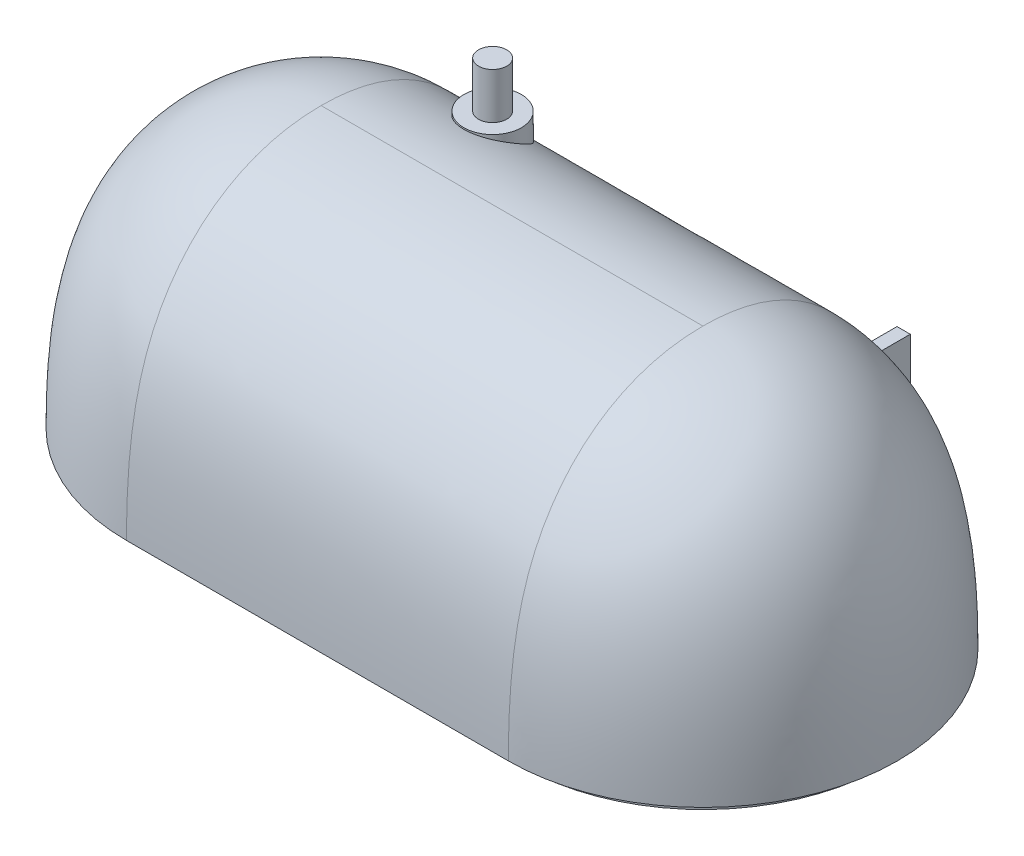
SolidWorks part; units mm, degrees
ref_plane "Front Plane" through (0, 0, 0) normal (0, 0, 1) x (1, 0, 0)
ref_plane "Top Plane" through (0, 0, 0) normal (0, 1, 0) x (1, 0, 0)
ref_plane "Right Plane" through (0, 0, 0) normal (1, 0, 0) x (0, 0, -1)
sketch "Sketch1" plane through (0, 0, 0) normal (0, 1, 0) x (1, 0, 0)
  line L0 (-41.915, 0) -> (41.915, 0) construction
  line L1 (-20.745, -21.17) -> (20.745, -21.17)
  line L2 (-20.745, -21.17) -> (-20.745, 21.17) construction
  line L3 (-20.745, 21.17) -> (20.745, 21.17)
  line L4 (20.745, -21.17) -> (20.745, 21.17) construction
  line L5 (-20.745, -21.17) -> (20.745, 21.17) construction
  line L6 (-20.745, 21.17) -> (20.745, -21.17) construction
  arc A0 (-20.745, -21.17) -> (-20.745, 21.17) centre (-20.745, 0) cw
  arc A1 (20.745, 21.17) -> (20.745, -21.17) centre (20.745, 0) cw
  point P0 (0, 0)
  dimension "D1" = 83.83
  dimension "D2" = 42.34
sketch "Sketch2" plane through (0, 0, 0) normal (1, 0, 0) x (0, 0, -1)
  line L0 (21.17, 0) -> (-21.17, 0) construction
  line L1 (21.17, 0) -> (-21.17, 0) construction
  line L2 (0, 0) -> (0, 31.55) construction
  line L3 (19.735, 0) -> (19.735, 1.19)
  line L4 (19.735, 1.19) -> (21.135, 1.19)
  line L5 (-19.735, 0) -> (19.735, 0)
  line L6 (-19.735, 1.19) -> (-21.135, 1.19)
  line L7 (-19.735, 0) -> (-19.735, 1.19)
  line L8 (18.1, 19.85) -> (18.1, 0) construction
  line L9 (18.1, 19.85) -> (-18.1, 19.85) construction
  line L10 (21.135, 1.19) -> (21.135, 0.6886) construction
  spline S0 degree 3 poles (21.135, 1.19) (21.135, 7.0764) (20.4011, 21.9995) (8.9089, 31.55) (0, 31.55) knots 0 0 0 0 0.467286 1 1 1 1
  spline S1 degree 3 poles (-21.135, 1.19) (-21.135, 7.0764) (-20.4011, 21.9995) (-8.9089, 31.55) (0, 31.55) knots 0 0 0 0 0.467286 1 1 1 1
  point P8 (0, 19.85)
  dimension "D1" = 31.55
  dimension "D2" = 39.47
  dimension "D3" = 1.19
  dimension "D4" = 1.4
  dimension "D5" = 36.2
  dimension "D6" = 19.85
extrude "Boss-Extrude2" add sketch "Sketch2" along normal up to vertex (20.745 mm away) and the other way up to vertex (20.745 mm away) up to point (20.745, 0, 21.17) other way up to point (-20.745, 0, 21.17)
sketch "Sketch4" plane through (-20.745, 0, 0) normal (-1, 0, 0) x (0, 0, 1)
  line L0 (0, 31.55) -> (0, 0)
  line L5 (-19.735, 1.19) -> (-19.735, 0)
  line L6 (-21.135, 1.19) -> (-19.735, 1.19)
  line L7 (19.735, 1.19) -> (21.135, 1.19)
  line L8 (19.735, 0) -> (19.735, 1.19)
  line L9 (-19.735, 0) -> (19.735, 0)
  line L12 (19.735, 1.19) -> (21.135, 1.19)
  line L13 (19.735, 0) -> (19.735, 1.19)
  line L14 (0, 0) -> (19.735, 0)
  spline S2 degree 3 poles (333.5549, -911.1802) (140.1511, 42.8638) (-153.2404, 81.7088) (86.9036, -145.8898) (-639.1994, 787.2913) knots -2.804305 -2.804305 -2.804305 -2.804305 0.532714 4.237911 4.237911 4.237911 4.237911 only from (0, 31.55) to (-21.135, 1.19)
  spline S3 degree 3 poles (2506.664, 3134.8984) (-251.1944, -284.8739) (340.5877, 177.8042) (-353.3586, -1.6005) (-731.6989, -3883.5105) knots -5.099916 -5.099916 -5.099916 -5.099916 0.467286 5.832152 5.832152 5.832152 5.832152 only from (21.135, 1.19) to (0, 31.55)
  spline S5 degree 3 poles (21.135, 1.19) (21.135, 7.0764) (20.4011, 21.9995) (8.9089, 31.55) (0, 31.55) knots 0 0 0 0 0.467286 1 1 1 1
  dimension "D1" = 0
revolve "Revolve2" add sketch "Sketch4" angle 180 about L0
mirror "Mirror2" about plane through (0, 0, 0) normal (1, 0, 0) of "Revolve2"
ref_plane "Plane1" through (0, 5.16, 0) normal (0, 1, 0) x (1, 0, 0)
sketch "Sketch5" plane through (0, 5.16, 0) normal (0, 1, 0) x (1, 0, 0)
  line L0 (20.745, 21.135) -> (-20.745, 21.135) construction
  line L1 (-21.34, 16.935) -> (-19.9, 16.935)
  line L2 (-21.34, 16.935) -> (-21.34, 21.935)
  line L3 (-21.34, 21.935) -> (-19.9, 21.935)
  line L4 (-19.9, 16.935) -> (-19.9, 21.935)
  line L5 (0, 0) -> (0, 16.9405) construction
  line L6 (19.9, 16.935) -> (19.9, 21.935)
  line L7 (21.34, 21.935) -> (19.9, 21.935)
  line L8 (21.34, 16.935) -> (21.34, 21.935)
  line L9 (21.34, 16.935) -> (19.9, 16.935)
  dimension "D1" = 5
  dimension "D2" = 0.8
  dimension "D3" = 1.44
  dimension "D4" = 39.8
extrude "Boss-Extrude3" add sketch "Sketch5" along normal blind 14.95
sketch "Sketch7" plane through (0, 5.16, 0) normal (0, 1, 0) x (1, 0, 0)
  line L0 (-14.9, 9.67) -> (-19.9, 9.67) construction
  line L1 (-19.9, 9.67) -> (-19.9, 17.9774) construction
  line L2 (-11.775, 12.795) -> (-11.775, 21.135) construction
  line L3 (20.745, 21.135) -> (-20.745, 21.135) construction
  circle A0 centre (-11.775, 9.67) radius 3.125
  dimension "D1" = 6.25
  dimension "D2" = 5
  dimension "D3" = 8.34
extrude "Boss-Extrude4" add sketch "Sketch7" along normal offset from surface (25.52 mm away) 30.68 up to plane "Top Plane"
sketch "Sketch8" plane through (0, 30.68, 0) normal (0, 1, 0) x (1, 0, 0)
  circle A0 centre (-11.775, 9.67) radius 1.535
  dimension "D1" = 3.07
extrude "Boss-Extrude5" add sketch "Sketch8" along normal blind 5
